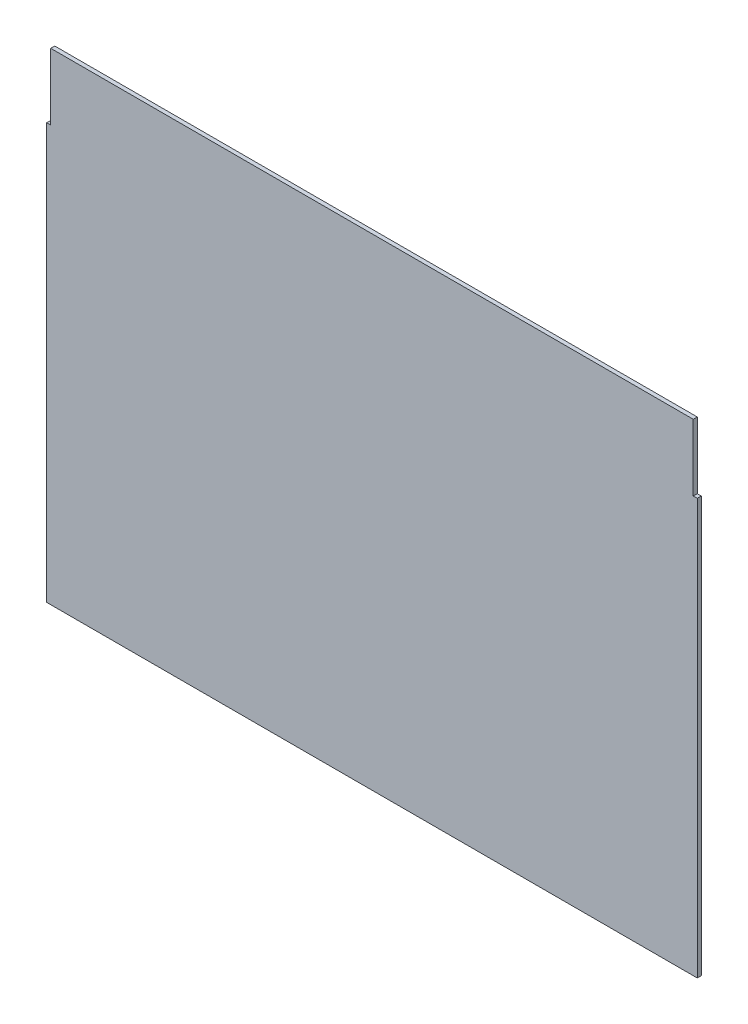
SolidWorks part; units mm, degrees
ref_plane "Front Plane" through (0, 0, 0) normal (0, 0, 1) x (1, 0, 0)
ref_plane "Top Plane" through (0, 0, 0) normal (0, 1, 0) x (1, 0, 0)
ref_plane "Right Plane" through (0, 0, 0) normal (1, 0, 0) x (0, 0, -1)
sketch "Sketch1" plane through (0, 0, 0) normal (0, 0, 1) x (1, 0, 0)
  line L1 (-254, -190.5) -> (254, -190.5)
  line L2 (-254, -190.5) -> (-254, 190.5)
  line L3 (-254, 190.5) -> (254, 190.5)
  line L4 (254, -190.5) -> (254, 190.5)
  line L5 (-254, -190.5) -> (254, 190.5) construction
  line L6 (-254, 190.5) -> (254, -190.5) construction
  point P0 (0, 0)
  dimension "D1" = 508
  dimension "D2" = 381
extrude "Boss-Extrude1" add sketch "Sketch1" along normal blind 3.175
sketch "Sketch3" plane through (0, 0, 3.175) normal (0, 0, 1) x (1, 0, 0)
  line L0 (-254, 190.5) -> (-254, -190.5) construction
  line L1 (-46.99, 77.47) -> (-39.37, 77.47)
  line L2 (-46.99, 77.47) -> (-46.99, 96.52)
  line L3 (-46.99, 96.52) -> (-39.37, 96.52)
  line L4 (-39.37, 77.47) -> (-39.37, 96.52)
  line L5 (254, 190.5) -> (-254, 190.5) construction
  dimension "D1" = 207.01
  dimension "D2" = 7.62
  dimension "D3" = 113.03
  dimension "D4" = 19.05
extrude "Cut-Extrude2" [suppressed] cut sketch "Sketch3" against normal up to surface (3.175 mm away) up to face at (0, 0, 0)
sketch "Sketch2" [suppressed] plane through (0, 0, 3.175) normal (0, 0, 1) x (1, 0, 0)
  line L0 (-250.825, 190.5) -> (-250.825, -190.5) construction
  line L1 (254, 190.5) -> (-254, 190.5) construction
  line L2 (-254, -190.5) -> (254, -190.5) construction
  line L3 (250.825, 190.5) -> (250.825, -190.5) construction
  line L4 (254, -190.5) -> (254, 190.5) construction
  line L5 (-254, 190.5) -> (-254, -190.5) construction
  line L6 (0, 0) -> (0, -50000) construction
  line L8 (-39.37, 96.52) -> (-46.99, 96.52) construction
  circle A0 centre (-250.825, -184.15) radius 1.8542
  circle A1 centre (-250.825, 184.15) radius 1.8542
  circle A2 centre (250.825, 184.15) radius 1.8542
  circle A3 centre (250.825, -184.15) radius 1.8542
  circle A4 centre (-250.825, 24.13) radius 1.8542
  circle A5 centre (250.825, 24.13) radius 1.8542
  circle A6 centre (-250.825, 11.43) radius 1.8542
  circle A7 centre (-250.825, -148.59) radius 1.8542
  circle A8 centre (-250.825, -161.29) radius 1.8542
  circle A9 centre (250.825, -161.29) radius 1.8542
  circle A10 centre (250.825, -148.59) radius 1.8542
  circle A11 centre (250.825, 11.43) radius 1.8542
  circle A12 centre (-79.7747, 110.49) radius 1.905
  circle A13 centre (-79.7747, 41.91) radius 1.905
  circle A14 centre (-61.9947, 110.49) radius 1.905
  circle A15 centre (-61.9947, 41.91) radius 1.905
  point P33 (0, -190.5)
  dimension "D3" = 3.7084
  dimension "D10" = 12.7
  dimension "D14" = 3.81
  dimension "D12" = 17.78
  dimension "D1" = 3.175
  dimension "D2" = 3.175
  dimension "D4" = 6.35
  dimension "D5" = 6.35
  dimension "D6" = 6.35
  dimension "D7" = 6.35
  dimension "D8" = 160.02
  dimension "D9" = 160.02
  dimension "D11" = 29.21
  dimension "D13" = 68.58
  dimension "D15" = 15.0047
  dimension "D16" = 13.97
extrude "Cut-Extrude1" [suppressed] cut sketch "Sketch2" against normal blind 3.175
sketch "Sketch4" plane through (0, 0, 3.175) normal (0, 0, 1) x (1, 0, 0)
  line L0 (254, -190.5) -> (254, 190.5) construction
  line L1 (254, 137.9538) -> (257.175, 137.9538)
  line L2 (254, 137.9538) -> (254, -190.5)
  line L3 (254, -190.5) -> (257.175, -190.5)
  line L4 (257.175, 137.9538) -> (257.175, -190.5)
  line L5 (-254, -190.5) -> (254, -190.5) construction
  line L6 (254, 190.5) -> (-254, 190.5) construction
  line L7 (0, 190.5) -> (0, -190.5) construction
  line L8 (-254, -190.5) -> (-257.175, -190.5)
  line L9 (-254, 137.9538) -> (-257.175, 137.9538)
  line L10 (-254, 137.9538) -> (-254, -190.5)
  line L11 (-257.175, 137.9538) -> (-257.175, -190.5)
  dimension "D1" = 3.175
  dimension "D2" = 52.5463
extrude "Boss-Extrude2" add sketch "Sketch4" against normal blind 3.175
